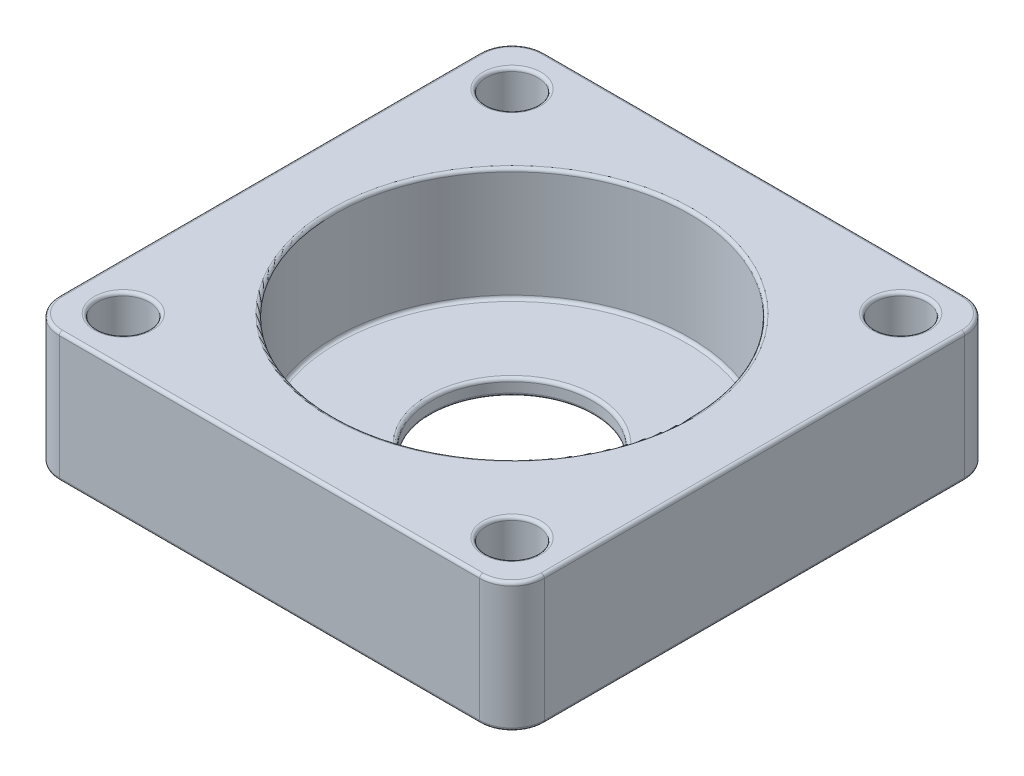
SolidWorks part; units mm, degrees
ref_plane "Front Plane" through (0, 0, 0) normal (0, 0, 1) x (1, 0, 0)
ref_plane "Top Plane" through (0, 0, 0) normal (0, 1, 0) x (1, 0, 0)
ref_plane "Right Plane" through (0, 0, 0) normal (1, 0, 0) x (0, 0, -1)
sketch "Sketch1" plane through (0, 0, 0) normal (0, 1, 0) x (1, 0, 0)
  line L0 (0, 0) -> (-17, 0) construction
  line L1 (-15, 15) -> (15, 15)
  line L2 (-15, 15) -> (-15, -15)
  line L3 (-15, -15) -> (15, -15)
  line L4 (15, 15) -> (15, -15)
  line L5 (-15, 15) -> (15, -15) construction
  line L6 (-15, -15) -> (15, 15) construction
  circle A0 centre (0, 0) radius 17 construction
  circle A1 centre (-12.0208, 12.0208) radius 1.6
  circle A2 centre (12.0208, 12.0208) radius 1.6
  circle A3 centre (12.0208, -12.0208) radius 1.6
  circle A4 centre (-12.0208, -12.0208) radius 1.6
  circle A5 centre (0, 0) radius 5
  circle A6 centre (0, 0) radius 11
  point P0 (0, 0)
  dimension "D3" = 10
  dimension "D4" = 22
  dimension "D1" = 30
  dimension "D2" = 30
extrude "Boss-Extrude1" add sketch "Sketch1" against normal blind 8 contours L4 L1 L2 L3 A6 A3 A2 A1 A4 | A6 A5 region at (0, 0, -14.5757) region at (-10.6889, 0, 0)
extrude "Cut-Extrude1" cut sketch "Sketch1<3>" against normal blind 7 contours A6 A5 region at (-10.6889, 0, 0)
sketch "Sketch1<3>" plane through (0, 0, 0) normal (0, 1, 0) x (1, 0, 0) same geometry as "Sketch1"
fillet "Fillet1" radius 2 4 edges at (15, -4, 15) (-15, -4, 15) (-15, -4, -15) (15, -4, -15)
fillet "Fillet2" radius 0.2 28 edges at (0, -8, 5) (-12.0208, -8, 13.6208) (14.4142, -8, -14.4142) (0, -8, -15) (-14.4142, -8, -14.4142) (-15, -8, 0) (-14.4142, -8, 14.4142) (0, -8, 15) (14.4142, -8, 14.4142) (15, -8, 0) (-12.0208, -8, -10.4208) (12.0208, -8, -10.4208) (12.0208, -8, 13.6208) (0, -7, 11) (0, -7, 5) (-12.0208, 0, 13.6208) (-14.4142, 0, 14.4142) (-15, 0, 0) (-14.4142, 0, -14.4142) (0, 0, -15) (14.4142, 0, -14.4142) (15, 0, 0) (14.4142, 0, 14.4142) (0, 0, 15) (-12.0208, 0, -10.4208) (12.0208, 0, -10.4208) (12.0208, 0, 13.6208) (0, 0, 11)
